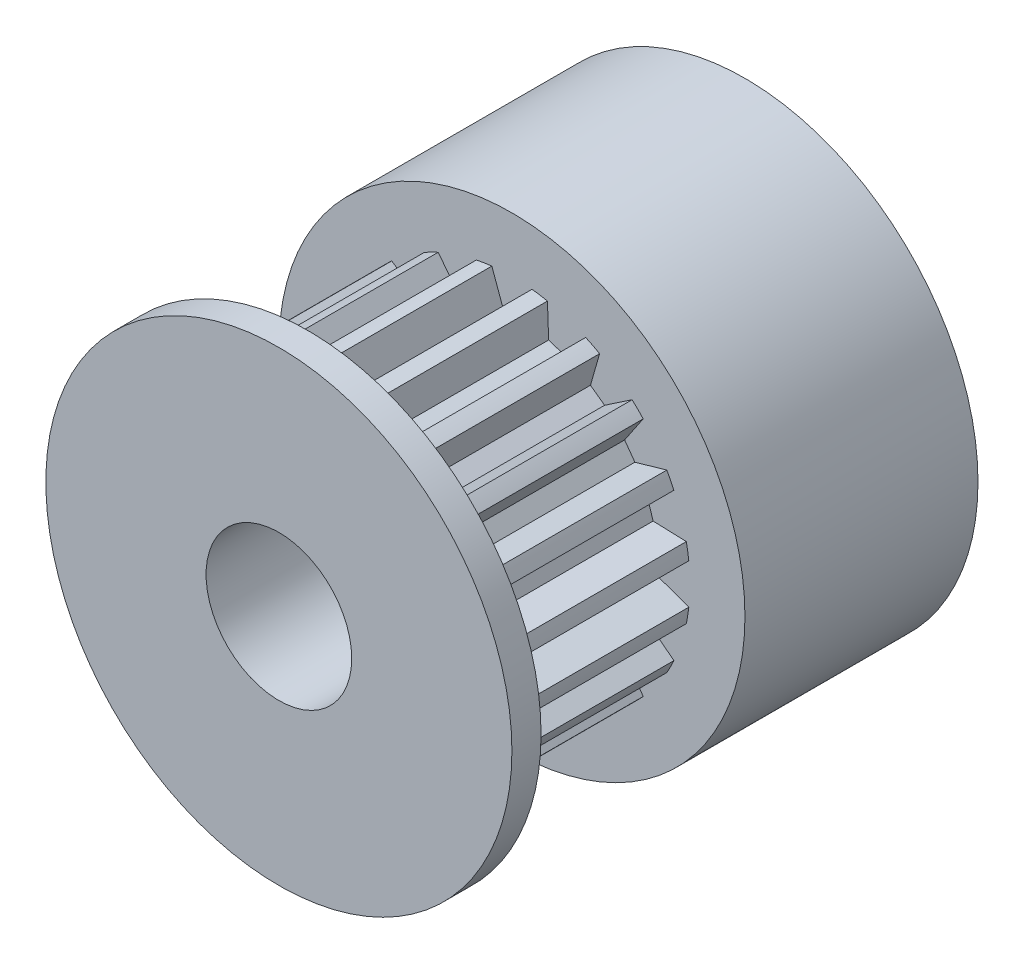
SolidWorks part; units mm, degrees
note: The reader was unsure of these and kept them because the rebuilt part matched: shared geometry of "Эскиз1<3>".
ref_plane "Спереди" through (0, 0, 0) normal (0, 0, 1) x (1, 0, 0)
ref_plane "Сверху" through (0, 0, 0) normal (0, 1, 0) x (1, 0, 0)
ref_plane "Справа" through (0, 0, 0) normal (1, 0, 0) x (0, 0, -1)
sketch "Эскиз1" plane through (0, 0, 0) normal (0, 0, 1) x (1, 0, 0)
  circle A0 centre (0, 0) radius 8
  circle A1 centre (0, 0) radius 2.5
  circle A2 centre (0, 0) radius 6.11
  dimension "D1" = 5
  dimension "D2" = 16
  dimension "D3" = 12.22
extrude "Бобышка-Вытянуть1" add sketch "Эскиз1" along normal blind 16 contours A2 A1
extrude "Бобышка-Вытянуть2" add sketch "Эскиз1<3>" along normal blind 8 contours A0 A2
sketch "Эскиз1<3>" plane through (0, 0, 0) normal (0, 0, 1) x (1, 0, 0) same geometry as "Эскиз1"
sketch "Эскиз2" plane through (0, 0, 16) normal (0, 0, 1) x (1, 0, 0)
  circle A0 centre (0, 0) radius 8 construction
  circle A1 centre (0, 0) radius 6.11
  circle A2 centre (0, 0) radius 6.11
  circle A3 centre (0, 0) radius 8
  dimension "D1" = 0
extrude "Бобышка-Вытянуть3" add sketch "Эскиз2" against normal blind 1
sketch "Эскиз3" plane through (0, 0, 8) normal (0, 0, 1) x (1, 0, 0)
  line L0 (0, 0) -> (0, 17.4349) construction
  line L1 (-0.7039, 6.1096) -> (-0.3, 5)
  line L2 (-0.3, 5) -> (0.3, 5)
  line L3 (0.3, 5) -> (0.7039, 6.1096)
  line L4 (0.7039, 6.1096) -> (0.828, 6.57)
  line L5 (0.828, 6.57) -> (-0.8044, 6.5004)
  line L6 (-0.8044, 6.5004) -> (-0.7039, 6.1096)
  line L7 (-0.7039, 6.1096) -> (-0.6997, 6.1204)
  circle A0 centre (0, 0) radius 6.15
  circle A1 centre (0, 0) radius 8
  circle A2 centre (0, 0) radius 8
  dimension "D2" = 12.3
  dimension "D3" = 0.6
  dimension "D4" = 0.3
  dimension "D5" = 5
  dimension "D6" = 110
  dimension "D7" = 110
  dimension "D1" = 0
extrude "Вырез-Вытянуть5" cut sketch "Эскиз3" along normal up to surface (7 mm away)
pattern_circular "Круговой массив1" count 20 over 360 about axis through (0, 0, 0) along (0, 0, 1) of "Вырез-Вытянуть5"
